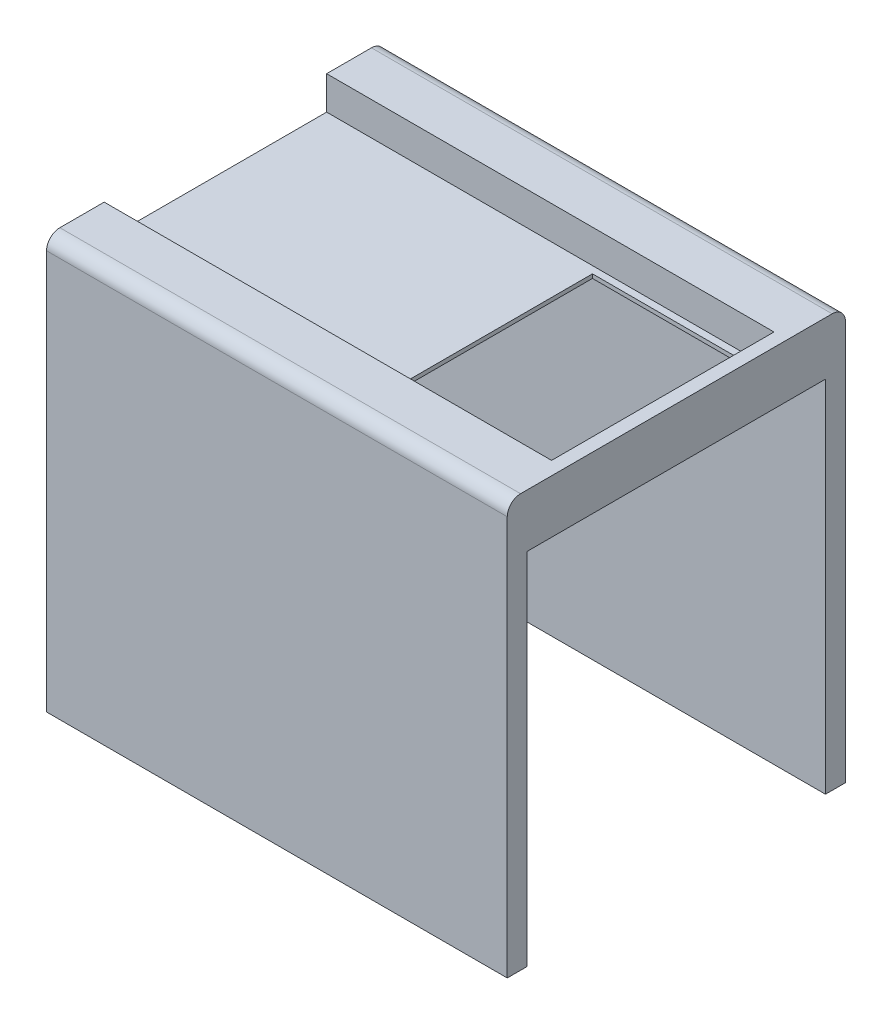
SolidWorks part; units mm, degrees
ref_plane "Front Plane" through (0, 0, 0) normal (0, 0, 1) x (1, 0, 0)
ref_plane "Top Plane" through (0, 0, 0) normal (0, 1, 0) x (1, 0, 0)
ref_plane "Right Plane" through (0, 0, 0) normal (1, 0, 0) x (0, 0, -1)
sketch "Sketch1" plane through (0, 0, 0) normal (0, 1, 0) x (1, 0, 0)
  line L1 (0, 0) -> (165, 0)
  line L2 (0, 0) -> (0, 82)
  line L3 (0, 82) -> (165, 82)
  line L4 (165, 0) -> (165, 82)
  line L5 (100, 2) -> (163, 2)
  line L6 (100, 2) -> (100, 80)
  line L7 (100, 80) -> (163, 80)
  line L8 (163, 2) -> (163, 80)
  line L9 (-2.5, -2.5) -> (167.5, -2.5)
  line L10 (-2.5, -2.5) -> (-2.5, 84.5)
  line L11 (-2.5, 84.5) -> (167.5, 84.5)
  line L12 (167.5, -2.5) -> (167.5, 84.5)
  dimension "D1" = 165
  dimension "D2" = 82
  dimension "D3" = 2
  dimension "D4" = 2
  dimension "D5" = 2
  dimension "D6" = 65
  dimension "D7" = 2.5
  dimension "D8" = 2.5
  dimension "D9" = 2.5
  dimension "D10" = 170
extrude "Boss-Extrude1" add sketch "Sketch1" along normal blind 2 contours L9 L12 L11 L10
extrude "Boss-Extrude5" add sketch "Sketch1<9>" along normal blind 2 separate body contours L9 L12 L11 L10
sketch "Sketch1<9>" plane through (0, 0, 0) normal (0, 1, 0) x (1, 0, 0) same geometry as "Sketch1"
extrude "Cut-Extrude3" cut sketch "Sketch1<10>" along normal blind 9 contours L6 L7 L8 L5
sketch "Sketch1<10>" plane through (0, 0, 0) normal (0, 1, 0) x (1, 0, 0) same geometry as "Sketch1"
extrude "Boss-Extrude6" add sketch "Sketch1<12>" along normal blind 14 contours L11 L12 L9 L10
sketch "Sketch1<12>" plane through (0, 0, 0) normal (0, 1, 0) x (1, 0, 0) same geometry as "Sketch1"
extrude "Cut-Extrude4" cut sketch "Sketch1<13>" along normal blind 10 contours L7 L8 L5 L6
sketch "Sketch1<13>" plane through (0, 0, 0) normal (0, 1, 0) x (1, 0, 0) same geometry as "Sketch1"
sketch "Sketch8" plane through (-2.5, 0, 0) normal (-1, 0, 0) x (0, 0, 1)
  line L0 (2.5, 14) -> (-84.5, 14) construction
  line L1 (-82.6737, 14) -> (0.8523, 14)
  line L2 (-82.6737, 14) -> (-82.6737, 1.5)
  line L3 (-82.6737, 1.5) -> (0.8523, 1.5)
  line L4 (0.8523, 14) -> (0.8523, 1.5)
  line L5 (2.5, 0) -> (-84.5, 0) construction
  dimension "D1" = 0
  dimension "D2" = 1.5
extrude "Cut-Extrude5" cut sketch "Sketch8" against normal blind 168 contours L3 L4 L1 L2
sketch "Sketch11" plane through (0, 0, 2.5) normal (0, 0, 1) x (1, 0, 0)
  line L1 (-2.5, 14) -> (90, 14)
  line L3 (-2.5, 9) -> (90, 9)
  line L5 (90, 14) -> (167.5, 14)
  line L6 (167.5, 14) -> (167.5, 9)
  line L7 (167.5, 14) -> (167.5, 0) construction
  line L8 (167.5, 9) -> (90, 9)
  line L9 (-2.5, 14) -> (-2.5, 9)
  dimension "D4" = 5
extrude "Boss-Extrude10" add sketch "Sketch11" along normal blind 20 contours L3 L8 L6 L5 L1 L9
ref_plane "Plane11" through (0, 0, -41) normal (0, 0, 1) x (1, 0, 0)
mirror "Mirror10" about plane through (0, 0, -41) normal (0, 0, 1) of "Boss-Extrude10"
sketch "Sketch25" plane through (0, 9, 0) normal (0, -1, 0) x (1, 0, 0)
  line L0 (167.5, -104.5) -> (167.5, -84.5) construction
  line L1 (-2.5, -104.5) -> (167.5, -104.5)
  line L2 (-2.5, -104.5) -> (-2.5, -97)
  line L3 (-2.5, -97) -> (167.5, -97)
  line L4 (167.5, -104.5) -> (167.5, -97)
  dimension "D1" = 7.5
extrude "Boss-Extrude18" add sketch "Sketch25" along normal blind 150 contours L3 L4 L1 L2
sketch "Sketch28" plane through (0, 9, 0) normal (0, -1, 0) x (1, 0, 0)
  line L0 (-2.5, 22.5) -> (167.5, 22.5) construction
  line L1 (-2.5, 22.5) -> (167.5, 22.5)
  line L2 (-2.5, 22.5) -> (-2.5, 15)
  line L3 (-2.5, 15) -> (167.5, 15)
  line L4 (167.5, 22.5) -> (167.5, 15)
  line L5 (167.5, 22.5) -> (167.5, 2.5) construction
  dimension "D1" = 7.5
extrude "Boss-Extrude19" add sketch "Sketch28" along normal blind 150
sketch "Sketch29" plane through (0, 9, 0) normal (0, -1, 0) x (1, 0, 0)
  line L0 (-2.5, 15) -> (-2.5, 2.5) construction
  line L1 (-2.5, 15) -> (-0.5, 15)
  line L2 (-2.5, 15) -> (-2.5, 2.5)
  line L3 (-2.5, 2.5) -> (-0.5, 2.5)
  line L4 (-0.5, 15) -> (-0.5, 2.5)
  line L5 (-2.5, 15) -> (167.5, 15) construction
  line L6 (-2.5, 2.5) -> (167.5, 2.5) construction
  line L7 (-2.5, 15) -> (167.5, 15) construction
  line L8 (165.5, 15) -> (167.5, 15)
  line L9 (165.5, 15) -> (165.5, 2.5)
  line L10 (165.5, 2.5) -> (167.5, 2.5)
  line L11 (167.5, 15) -> (167.5, 2.5)
  line L12 (167.5, 2.5) -> (167.5, -84.5) construction
  line L13 (-2.5, -97) -> (167.5, -97) construction
  line L14 (167.5, -84.5) -> (165.5, -84.5)
  line L15 (167.5, -84.5) -> (167.5, -97)
  line L16 (167.5, -97) -> (165.5, -97)
  line L17 (165.5, -84.5) -> (165.5, -97)
  line L19 (-2.5, -84.5) -> (-0.5, -84.5)
  line L20 (-2.5, -84.5) -> (-2.5, -97)
  line L21 (-2.5, -97) -> (-0.5, -97)
  line L22 (-0.5, -84.5) -> (-0.5, -97)
  dimension "D1" = 2
  dimension "D2" = 2
  dimension "D3" = 2
  dimension "D4" = 2
ref_plane "Plane14" through (82.5, 0, 0) normal (-1, 0, 0) x (0, 0, 1)
extrude "Boss-Extrude20" add sketch "Sketch29" along normal blind 15 contours L22 L21 L20 L19
mirror "Mirror16" about plane through (0, 0, -41) normal (0, 0, 1) of "Boss-Extrude20" second plane through (82.5, 0, 0) second plane normal (-1, 0, 0)
sketch "Sketch31" plane through (0, 0, 0) normal (0, -1, 0) x (1, 0, 0)
  line L1 (-0.5, 2.5) -> (-2.5, 2.5)
  line L2 (-0.5, 2.5) -> (-0.5, -84.5)
  line L3 (-0.5, -84.5) -> (-2.5, -84.5)
  line L4 (-2.5, 2.5) -> (-2.5, -84.5)
extrude "Boss-Extrude21" add sketch "Sketch31" along normal blind 6
mirror "Mirror17" about plane through (82.5, 0, 0) normal (-1, 0, 0) of "Boss-Extrude21"
sketch "Sketch34" plane through (167.5, 0, 0) normal (1, 0, 0) x (0, 0, -1)
  line L0 (-22.5, 14) -> (104.5, 14)
  line L1 (104.5, 14) -> (104.5, -141)
  line L2 (104.5, -141) -> (97, -141)
  line L3 (97, -141) -> (97, -6)
  line L4 (97, -6) -> (-15, -6)
  line L5 (-15, -6) -> (-15, -141)
  line L6 (-15, -141) -> (-22.5, -141)
  line L7 (-22.5, -141) -> (-22.5, 14)
extrude "Boss-Extrude22" add sketch "Sketch34" along normal blind 3
fillet "Fillet14" radius 5 4 edges at (84, 14, -104.5) (84, 14, 22.5) (82.5, 9, -97) (82.5, 9, 15)
delete or keep bodies "Body-Delete/Keep 1" type delete bodies bodies 101
